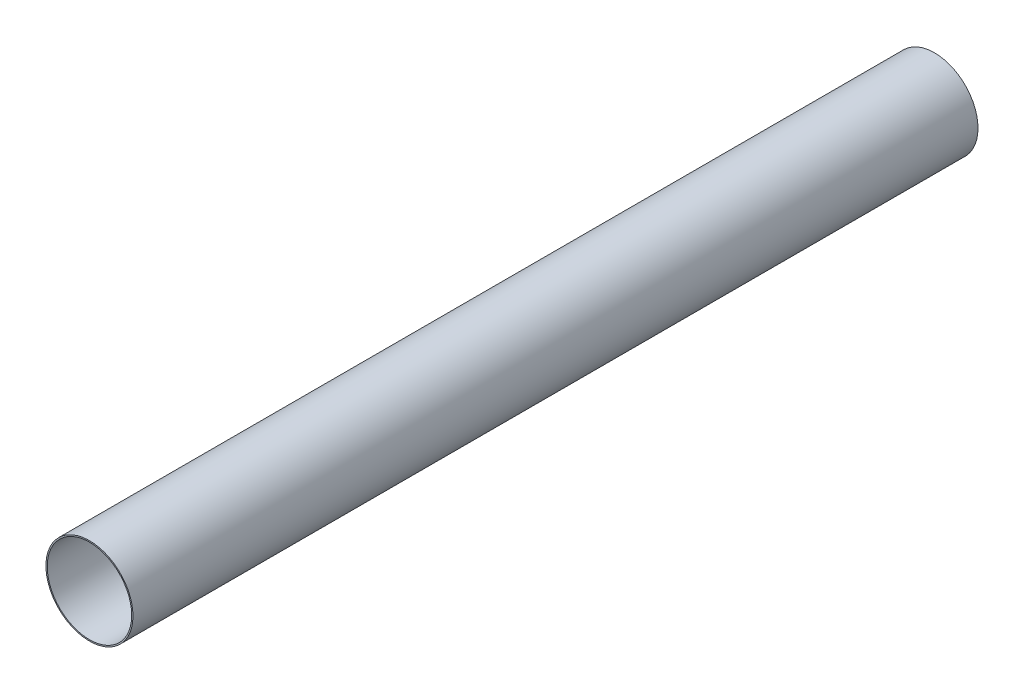
SolidWorks part; units mm, degrees
ref_plane "Front Plane" through (0, 0, 0) normal (0, 0, 1) x (1, 0, 0)
ref_plane "Top Plane" through (0, 0, 0) normal (0, 1, 0) x (1, 0, 0)
ref_plane "Right Plane" through (0, 0, 0) normal (1, 0, 0) x (0, 0, -1)
sketch "Sketch1" plane through (0, 0, 0) normal (0, 0, 1) x (1, 0, 0)
  circle A0 centre (0, 0) radius 39.2557
  circle A1 centre (0, 0) radius 38.1
  dimension "D2" = 78.5114
extrude "Boss-Extrude1" add sketch "Sketch1" along normal mid plane 762
equation "\"AIRFRAME_OD\"= 3.091in"
equation "\"AIRFRAME_ID\"= 3.00in"
equation "\"FLAT_T\" = 0.125in"
equation "\"NOSE_EXP_L\"= 3.5in"
equation "\"NOSE_SHOULDER_L\" = 5in"
equation "\"MAIN_L\" = 30in"
equation "\"RECO_COUP_L\" = 6in"
equation "\"RECO_SWITCH_L\" = 1.5in"
equation "\"DROGUE_L\" = 14in"
equation "\"ATS_FORE_COUP_L\" = 4in"
equation "\"ATS_AFT_COUP_L\" = 4in"
equation "\"LOWER_L\" = 16in"
equation "\"FIN_N\" = 4"
equation "\"CR_AFT_X\" = 0.5in"
equation "\"CR_FORE_X\" = 6in"
equation "\"D1@Sketch1\"=\"AIRFRAME_ID\""
equation "\"D2@Sketch1\"=\"AIRFRAME_OD\""
equation "\"D1@Boss-Extrude1\"=\"MAIN_L\""
equation "\"FIN_ROOT\" = 5in"
equation "\"FIN_X\" = 0.75in"
equation "\"MOTOR_OD\" = 2.25in"
equation "\"MOTOR_ID\" = 2.126in"
